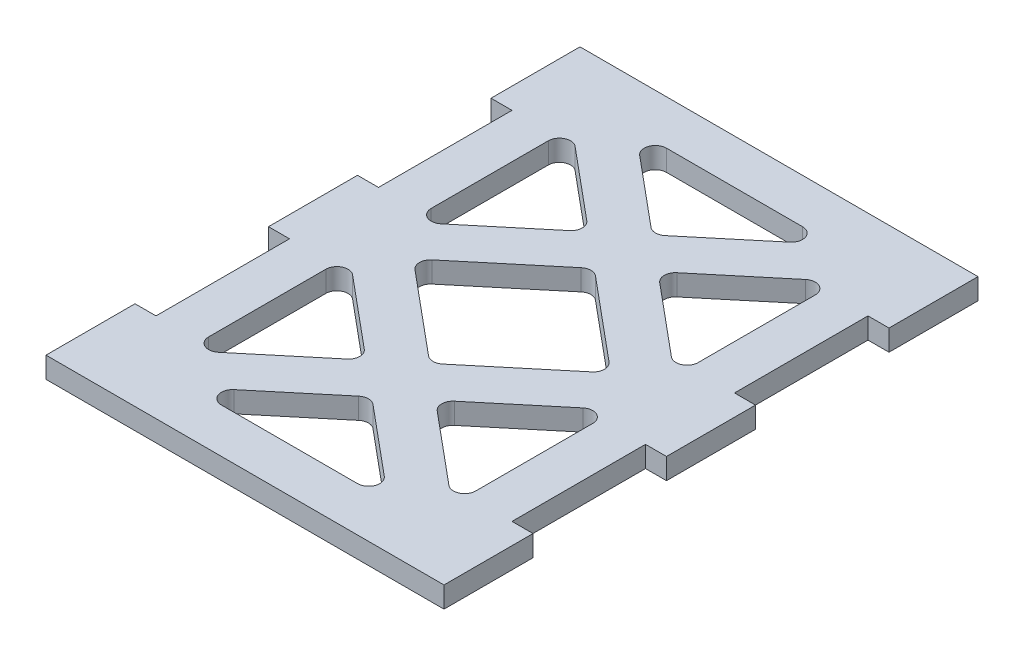
SolidWorks part; units mm, degrees
material "Custom Plastic"
ref_plane "Front Plane" through (0, 0, 0) normal (0, 0, 1) x (1, 0, 0)
ref_plane "Top Plane" through (0, 0, 0) normal (0, 1, 0) x (1, 0, 0)
ref_plane "Right Plane" through (0, 0, 0) normal (1, 0, 0) x (0, 0, -1)
sketch "Sketch1" plane through (0, 0, 0) normal (0, 1, 0) x (1, 0, 0)
  line L1 (-25.4, -38.1) -> (25.4, -38.1)
  line L2 (-25.4, -38.1) -> (-25.4, 38.1)
  line L3 (-25.4, 38.1) -> (25.4, 38.1)
  line L4 (25.4, -38.1) -> (25.4, 38.1)
  line L5 (-25.4, -38.1) -> (25.4, 38.1) construction
  line L6 (-25.4, 38.1) -> (25.4, -38.1) construction
  point P0 (0, 0)
  dimension "D1" = 50.8
  dimension "D2" = 76.2
extrude "Boss-Extrude1" add sketch "Sketch1" along normal blind 2.9972
sketch "Sketch2" plane through (0, 2.9972, 0) normal (0, 1, 0) x (1, 0, 0)
  line L0 (25.4, 6.35) -> (28.3972, 6.35)
  line L1 (25.4, 38.1) -> (28.3972, 38.1)
  line L2 (25.4, 38.1) -> (25.4, 25.4)
  line L3 (25.4, 25.4) -> (28.3972, 25.4)
  line L4 (28.3972, 38.1) -> (28.3972, 25.4)
  line L5 (25.4, 6.35) -> (25.4, -6.35)
  line L6 (25.4, -6.35) -> (28.3972, -6.35)
  line L7 (28.3972, 6.35) -> (28.3972, -6.35)
  line L8 (25.4, -25.4) -> (28.3972, -25.4)
  line L9 (25.4, -25.4) -> (25.4, -38.1)
  line L10 (25.4, -38.1) -> (28.3972, -38.1)
  line L11 (28.3972, -25.4) -> (28.3972, -38.1)
  line L12 (-28.3972, 6.35) -> (-25.4, 6.35)
  line L13 (-28.3972, 6.35) -> (-28.3972, -6.35)
  line L14 (-28.3972, -6.35) -> (-25.4, -6.35)
  line L15 (-25.4, 6.35) -> (-25.4, -6.35)
  line L16 (-28.3972, -25.4) -> (-25.4, -25.4)
  line L17 (-28.3972, -25.4) -> (-28.3972, -38.1)
  line L18 (-28.3972, -38.1) -> (-25.4, -38.1)
  line L19 (-25.4, -25.4) -> (-25.4, -38.1)
  line L20 (-28.3972, 38.1) -> (-25.4, 38.1)
  line L21 (-28.3972, 38.1) -> (-28.3972, 25.4)
  line L22 (-28.3972, 25.4) -> (-25.4, 25.4)
  line L23 (-25.4, 38.1) -> (-25.4, 25.4)
  line L24 (25.4, -38.1) -> (25.4, 38.1) construction
  line L25 (-25.4, -38.1) -> (25.4, -38.1) construction
  dimension "D1" = 2.9972
  dimension "D2" = 12.7
  dimension "D3" = 3
  dimension "D4" = 2
extrude "Boss-Extrude2" add sketch "Sketch2" against normal blind 2.9972
sketch "Sketch3" plane through (0, 2.9972, 0) normal (0, 1, 0) x (1, 0, 0)
  line L0 (-25.4, -6.35) -> (-25.4, -25.4) construction
  line L1 (-19.05, 31.75) -> (19.05, 31.75)
  line L2 (-19.05, 31.75) -> (-19.05, -31.75)
  line L3 (-19.05, -31.75) -> (19.05, -31.75)
  line L4 (19.05, 31.75) -> (19.05, -31.75)
  line L5 (28.3972, 38.1) -> (-28.3972, 38.1) construction
  line L6 (25.4, 6.35) -> (25.4, 25.4) construction
  line L7 (-28.3972, -38.1) -> (28.3972, -38.1) construction
  dimension "D1" = 6.35
  dimension "D2" = 6.35
  dimension "D3" = 6.35
  dimension "D4" = 6.35
extrude "Cut-Extrude1" cut sketch "Sketch3" against normal through all
sketch "Sketch4" plane through (0, 2.9972, 0) normal (0, 1, 0) x (1, 0, 0)
  line L0 (-19.05, 31.75) -> (19.05, 0)
  line L1 (19.05, -31.75) -> (19.05, 31.75) construction
  line L2 (19.05, 0) -> (-19.05, -31.75)
  line L3 (19.05, -31.75) -> (-19.05, 0)
  line L4 (-19.05, 31.75) -> (-19.05, -31.75) construction
  line L5 (-19.05, 0) -> (19.05, 31.75)
extrude "Extrude-Thin1" add sketch "Sketch4" against normal up to surface (2.9972 mm away) thin up to face at (0, 0, 0) thin type mid plane wall 6.35
fillet "Fillet1" radius 1.5875 22 edges at (14.0905, 1.4986, 0) (-14.0905, 1.4986, 0) (0, 1.4986, 11.7421) (4.9595, 1.4986, 15.875) (19.05, 1.4986, 27.6171) (19.05, 1.4986, 4.1329) (-14.0905, 1.4986, -31.75) (0, 1.4986, -20.0079) (14.0905, 1.4986, -31.75) (19.05, 1.4986, -27.6171) (4.9595, 1.4986, -15.875) (19.05, 1.4986, -4.1329) (-19.05, 1.4986, -4.1329) (-4.9595, 1.4986, -15.875) (-19.05, 1.4986, -27.6171) (14.0905, 1.4986, 31.75) (0, 1.4986, 20.0079) (-14.0905, 1.4986, 31.75) (-4.9595, 1.4986, 15.875) (-19.05, 1.4986, 4.1329) (-19.05, 1.4986, 27.6171) (0, 1.4986, -11.7421)
